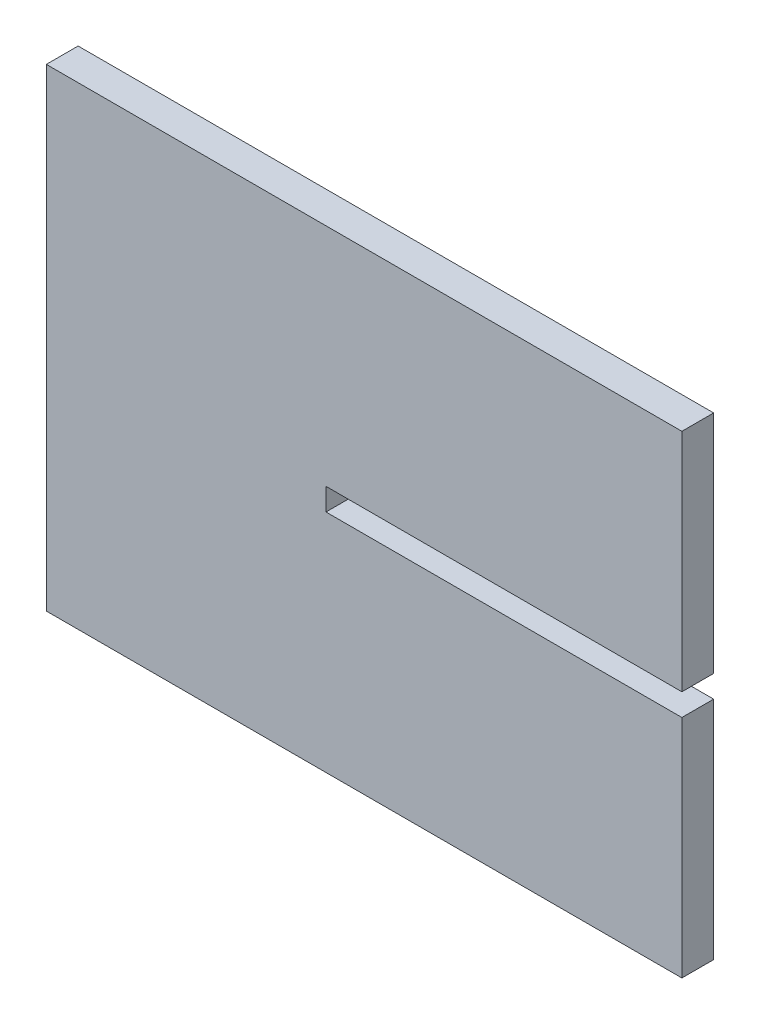
SolidWorks part; units mm, degrees
material "Простая углеродистая сталь"
ref_plane "Спереди" through (0, 0, 0) normal (0, 0, 1) x (1, 0, 0)
ref_plane "Сверху" through (0, 0, 0) normal (0, 1, 0) x (1, 0, 0)
ref_plane "Справа" through (0, 0, 0) normal (1, 0, 0) x (0, 0, -1)
sketch "Эскиз1" plane through (0, 0, 0) normal (0, 0, 1) x (1, 0, 0)
  line L0 (200, -78) -> (200, -149)
  line L1 (0, 0) -> (200, 0)
  line L2 (0, 0) -> (0, -149)
  line L3 (0, -149) -> (200, -149)
  line L4 (200, 0) -> (200, -71)
  line L5 (100, -149) -> (100, 0) construction
  line L6 (0, -74.5) -> (200, -74.5) construction
  line L7 (200, -71) -> (88, -71)
  line L9 (200, -78) -> (88, -78)
  line L10 (88, -71) -> (88, -78)
  line L11 (144, -78) -> (144, -71) construction
  line L12 (200, -74.5) -> (88, -74.5) construction
  point P144 (100, -74.5)
  point P270 (144, -74.5)
  dimension "D1" = 149
  dimension "D2" = 200
  dimension "D3" = 112
  dimension "D4" = 7
base flange "Базовая кромка1" sketch "Эскиз1" thickness 10 reverse thickness direction no parameters "D1"=1
sketch "Сгиб-Линии1" plane through (0, 0, 0) normal (0, 1, 0) x (1, 0, 0)
sketch "Граничная рамка1" plane through (0, 0, 0) normal (0, 1, 0) x (1, 0, 0)
sheet metal parameters "Листовой металл1" thickness 10 parameters "D1"=1
flat pattern "Развертка1" [suppressed]
sketch "Сгиб-Линии2" plane through (0, 0, 0) normal (0, 1, 0) x (1, 0, 0)
sketch3d "Граничная рамка2" [suppressed]
  line L0 (0, -149, 0) -> (200, -149, 0) construction
  line L1 (0, 0, 0) -> (200, 0, 0) construction
  line L2 (0, -149, 0) -> (0, 0, 0) construction
  line L3 (200, -149, 0) -> (200, 0, 0) construction
